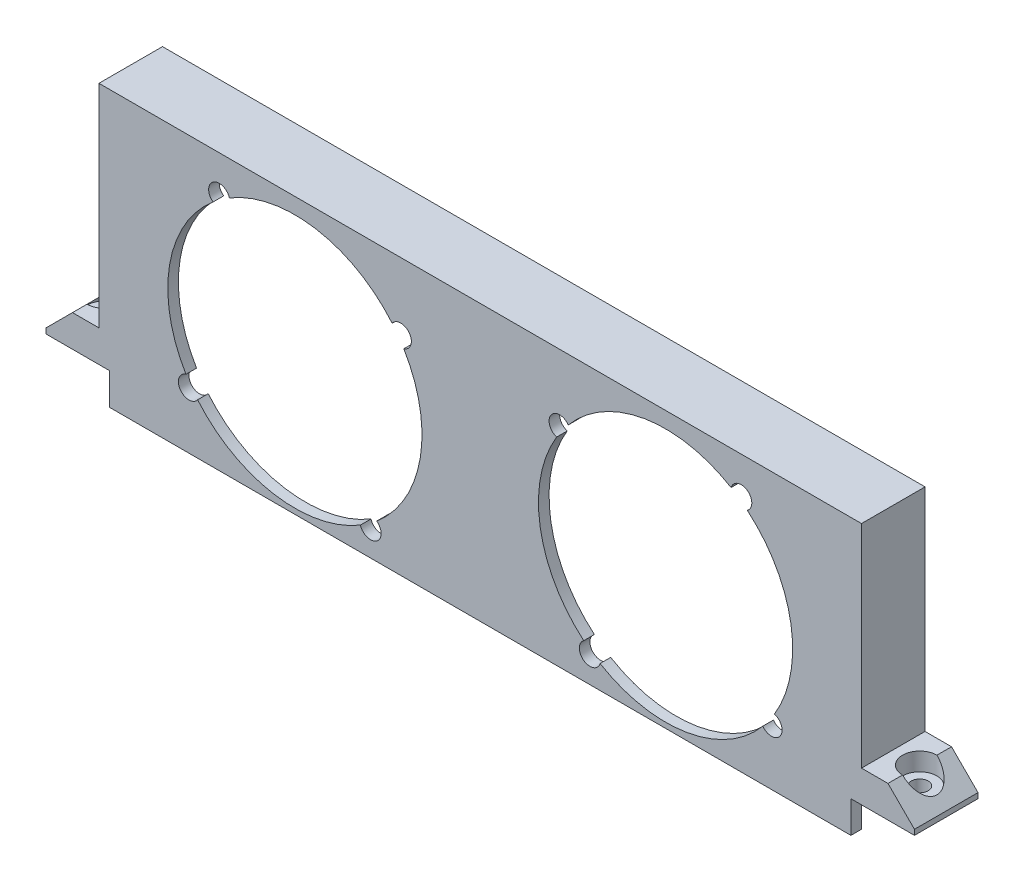
SolidWorks part; units mm, degrees
ref_plane "Front Plane" through (0, 0, 0) normal (0, 0, 1) x (1, 0, 0)
ref_plane "Top Plane" through (0, 0, 0) normal (0, 1, 0) x (1, 0, 0)
ref_plane "Right Plane" through (0, 0, 0) normal (1, 0, 0) x (0, 0, -1)
sketch "Szkic1" plane through (0, 0, 0) normal (0, 0, 1) x (1, 0, 0)
  line L0 (-70, -25) -> (70, 25) construction
  line L1 (-70, 25) -> (70, 25)
  line L2 (-70, 25) -> (-70, -25)
  line L3 (-70, -25) -> (70, -25)
  line L4 (70, 25) -> (70, -25)
  line L5 (0, 25) -> (0, -25) construction
  line L6 (0, 25) -> (-70, -25) construction
  circle A0 centre (-35, 0) radius 24
  circle A2 centre (-15, 14.2857) radius 2
  circle A3 centre (-20.7143, -20) radius 2
  circle A4 centre (-55, -14.2857) radius 2
  circle A5 centre (-49.2857, 20) radius 2
  circle A6 centre (35, 0) radius 24
  circle A7 centre (15, 14.2857) radius 2
  circle A8 centre (55, -14.2857) radius 2
  circle A9 centre (49.2857, 20) radius 2
  circle A10 centre (20.7143, -20) radius 2
  dimension "D4" = 48
  dimension "D6" = 4
  dimension "D1" = 50
  dimension "D2" = 140
  dimension "D3" = 20
  dimension "D5" = 4
extrude "Dodanie-wyciągnięcie1" add sketch "Szkic1" along normal blind 2 contours L4 L1 L2 L3 A9 A7 A0 A2 A3 A4 A5 A6 A8 A10 region at (0, 0, 0)
sketch "Szkic2" plane through (0, 0, 2) normal (0, 0, 1) x (1, 0, 0)
  line L0 (70, 25) -> (70, -25) construction
  line L1 (-70, -25) -> (70, -25) construction
  line L2 (-70, 25) -> (70, 25) construction
  line L3 (-70, 25) -> (-70, -25) construction
  line L4 (70, 25) -> (70, -25)
  line L5 (-70, -25) -> (70, -25)
  line L6 (-70, 25) -> (70, 25)
  line L7 (-70, 25) -> (-70, -25)
  line L8 (-72, 27) -> (72, 27)
  line L9 (72, 27) -> (72, -27)
  line L10 (-72, -27) -> (72, -27)
  line L11 (-72, 27) -> (-72, -27)
  line L12 (-72, -19) -> (72, -19)
  line L13 (0, -27) -> (0, 27) construction
  line L14 (-72, -19) -> (-82, -19)
  line L15 (-72, -19) -> (-72, -13)
  line L16 (-72, -13) -> (-82, -13)
  line L17 (-82, -19) -> (-82, -13)
  line L18 (72, -13) -> (82, -13)
  line L19 (82, -19) -> (82, -13)
  line L20 (72, -19) -> (82, -19)
  line L21 (72, -19) -> (72, -13)
  line M8 (70, 25) -> (-70, 25)
  line M9 (-70, 25) -> (-70, -25)
  dimension "D2" = 6
  dimension "D3" = 10
  dimension "D4" = 6
  dimension "D1" = 2
extrude "Dodanie-wyciągnięcie2" add sketch "Szkic2" against normal blind 12 contours L17 L14 L11 L16 | L6 L13 L8 L11 L12 M9 | L9 L20 L19 L18 | L13 L4 L12 L9 L8 M8 region at (35, 25.8544, 2) region at (-35, 25.8544, 2) region at (77, -16, 2) region at (-77, -16, 2)
hole_wizard "CBORE for M3 Hex Socket Head Cap Screw1" positions "Szkic3" profile "Szkic4" counterbore size "M3" standard "DIN"
sketch "Szkic3" plane through (0, -13, 0) normal (0, 1, 0) x (1, 0, 0)
  line L0 (-77, -2) -> (-77, 10) construction
  line L3 (-72, -2) -> (-82, -2) construction
  line L4 (-72, 10) -> (-82, 10) construction
  point P0 (-77, 4)
sketch "Szkic4" plane through (-77, -13, -4) normal (1, 0, 0) x (0, 0, 1)
  line L0 (0, 0) -> (0, 8.6614)
  line L1 (0, 8.6614) -> (1.6, 7.7)
  line L2 (1.6, 7.7) -> (1.6, 3.4)
  line L3 (1.6, 3.4) -> (3.25, 3.4)
  line L4 (3.25, 3.4) -> (3.25, 0)
  line L5 (3.25, 0) -> (0, 0)
  line L10 (0, 8.6614) -> (-1.6, 7.7) construction
  line L11 (0, -6.35) -> (0, 107.95) construction
  dimension "Hole Dia." = 3.2
  dimension "Hole Depth" = 7.7
  dimension "C'Bore Dia." = 6.5
  dimension "C'Bore Depth" = 3.4
  dimension "Drill Angle" = 118
mirror "Lustro1" about plane through (0, 0, 0) normal (1, 0, 0) of "CBORE for M3 Hex Socket Head Cap Screw1"
chamfer "Sfazowanie1" distance 5 angle 45 2 edges at (-82, -13, -4) (82, -13, -4)
